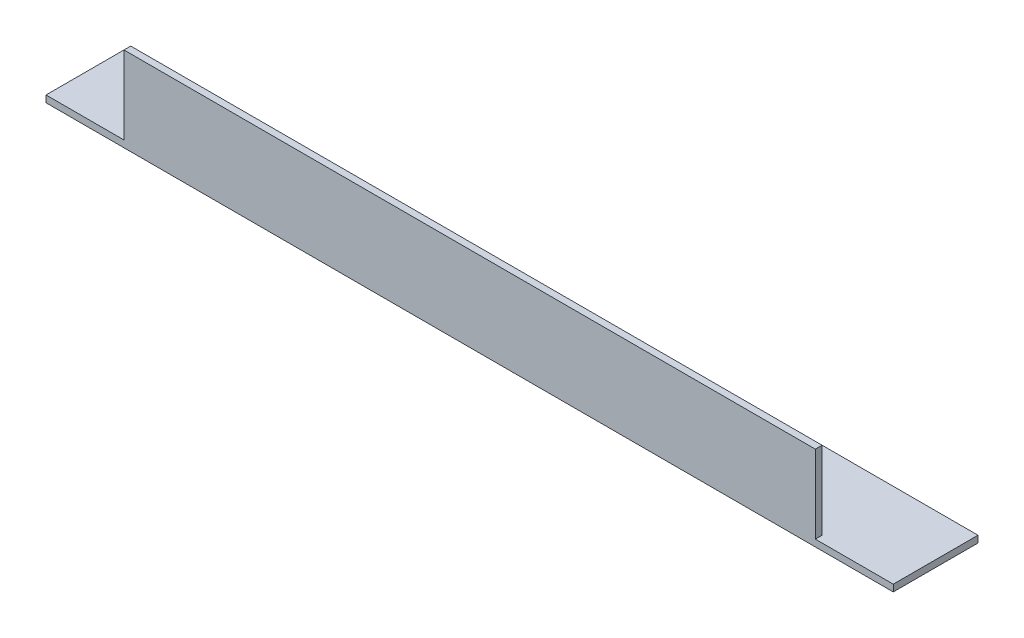
SolidWorks part; units mm, degrees
ref_plane "Спереди" through (0, 0, 0) normal (0, 0, 1) x (1, 0, 0)
ref_plane "Сверху" through (0, 0, 0) normal (0, 1, 0) x (1, 0, 0)
ref_plane "Справа" through (0, 0, 0) normal (1, 0, 0) x (0, 0, -1)
sketch "Эскиз1" plane through (0, 0, 0) normal (1, 0, 0) x (0, 0, -1)
  line L0 (0, 25) -> (0, 0)
  line L1 (0, 0) -> (25, 0)
extrude "Вытянуть-Тонкостенный1" add sketch "Эскиз1" along normal blind 250 thin thin type one direction reverse wall 2
sketch "Эскиз2" plane through (0, 0, 0) normal (0, 0, 1) x (1, 0, 0)
  line L0 (250, 0) -> (0, 0) construction
  line L1 (250, 25) -> (227, 25)
  line L2 (250, 25) -> (250, 2)
  line L3 (250, 2) -> (227, 2)
  line L4 (227, 25) -> (227, 2)
  line L6 (250, 25) -> (0, 25) construction
  line L7 (250, 25) -> (250, 0) construction
  line L8 (125, 43.7543) -> (125, -43.7543) construction
  line L9 (23, 25) -> (23, 2)
  line L10 (0, 2) -> (23, 2)
  line L11 (0, 25) -> (0, 2)
  line L12 (0, 25) -> (23, 25)
  point P16 (125, 0)
  dimension "D2" = 23
extrude "Вырез-Вытянуть1" cut sketch "Эскиз2" against normal through all
